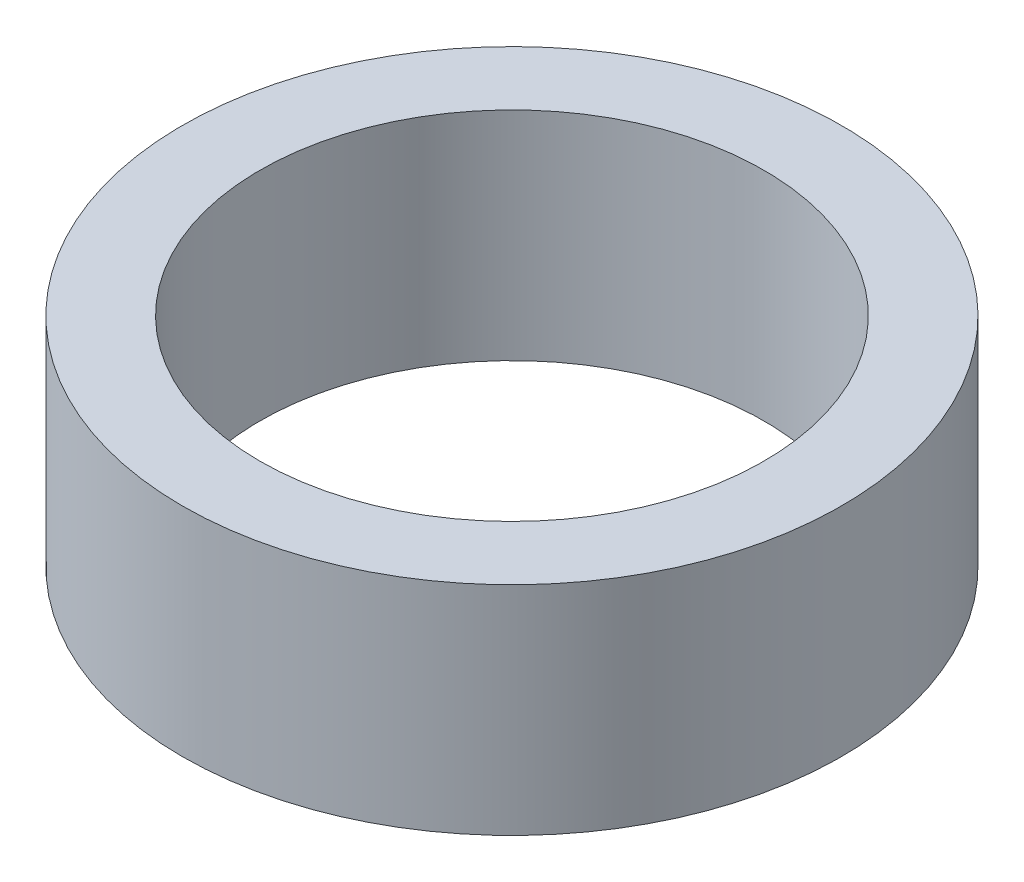
SolidWorks part; units mm, degrees
ref_plane "Front Plane" through (0, 0, 0) normal (0, 0, 1) x (1, 0, 0)
ref_plane "Top Plane" through (0, 0, 0) normal (0, 1, 0) x (1, 0, 0)
ref_plane "Right Plane" through (0, 0, 0) normal (1, 0, 0) x (0, 0, -1)
sketch "Sketch1" plane through (0, 0, 0) normal (0, 1, 0) x (1, 0, 0)
  circle A0 centre (0, 0) radius 42.5
  dimension "FLANGE_OD" = 85
extrude "Boss-Extrude1" add sketch "Sketch1" along normal blind 28
sketch "Sketch2" plane through (0, 0, 0) normal (0, 1, 0) x (1, 0, 0)
  circle A0 centre (0, 0) radius 32.5
  dimension "BORE_D" = 65
extrude "Cut-Extrude1" cut sketch "Sketch2" along normal through all
sketch "Sketch3" plane through (0, 28, 0) normal (0, 1, 0) x (1, 0, 0)
  circle A0 centre (0, 0) radius 19.5471 construction
  circle A1 centre (-19.5471, 0) radius 1.5261
  dimension "BOLT_D" = 3.0522
  dimension "BOLT_PCD" = 39.0942
extrude "Cut-Extrude2" cut sketch "Sketch3" against normal blind 25.4945 rebuild error yes
pattern_circular "CirPattern1" count 3 over 360 rebuild error yes
